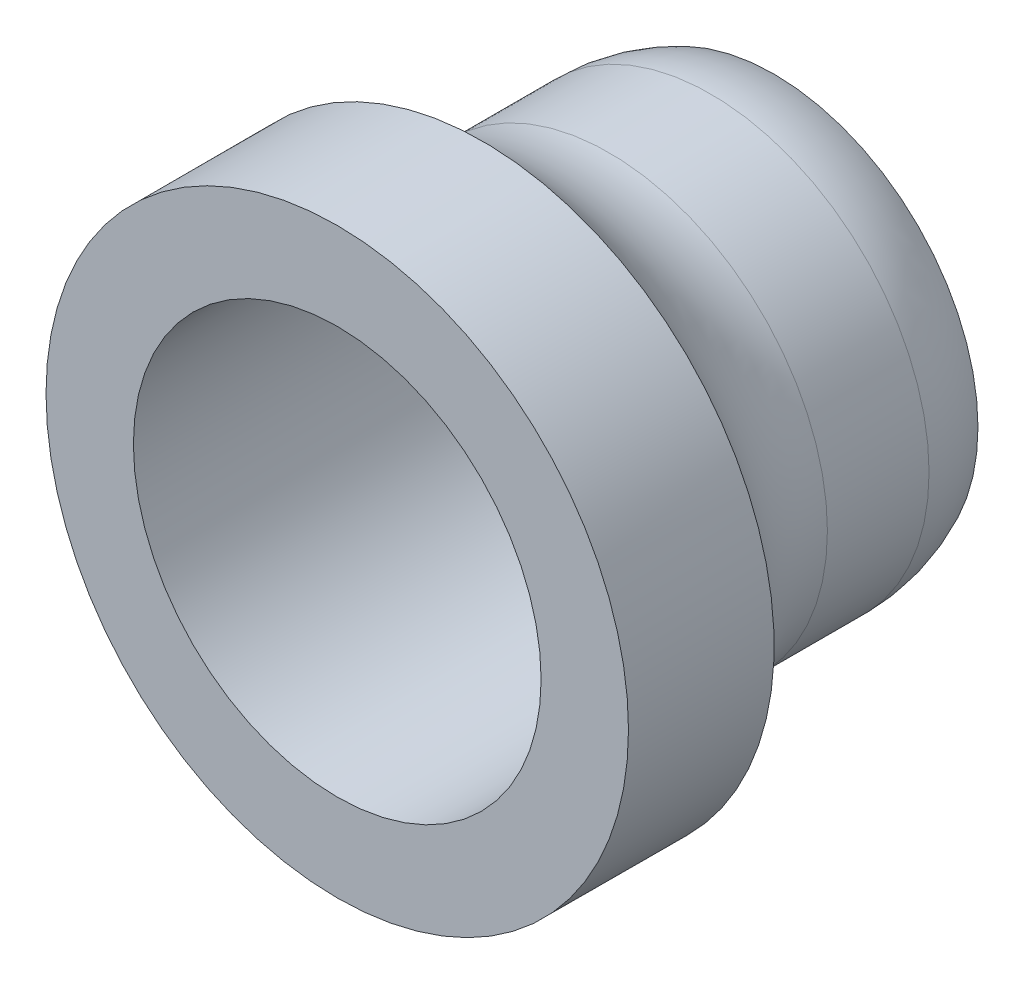
SolidWorks part; units mm, degrees
material "BUTYL"
ref_plane "Front Plane" through (0, 0, 0) normal (0, 0, 1) x (1, 0, 0)
ref_plane "Top Plane" through (0, 0, 0) normal (0, 1, 0) x (1, 0, 0)
ref_plane "Right Plane" through (0, 0, 0) normal (1, 0, 0) x (0, 0, -1)
sketch "Sketch1" plane through (0, 0, 0) normal (0, 0, 1) x (1, 0, 0)
  circle A0 centre (0, 0) radius 14
  circle A1 centre (0, 0) radius 20
extrude "Boss-Extrude1" add sketch "Sketch1" along normal blind 30
sketch "Sketch2" plane through (0, 0, 0) normal (0, 0, -1) x (-1, 0, 0)
  circle A1 centre (0, 0) radius 20
  circle A2 centre (0, 0) radius 15
extrude "Cut-Extrude1" cut sketch "Sketch2" against normal blind 20
fillet "Fillet1" radius 10 2 edges at (-15, 0, 0) (-15, 0, 20)
